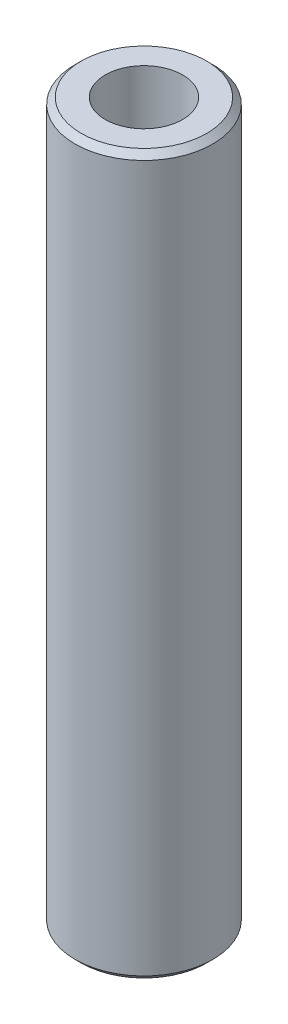
SolidWorks part; units mm, degrees
ref_plane "Front Plane" through (0, 0, 0) normal (0, 0, 1) x (1, 0, 0)
ref_plane "Top Plane" through (0, 0, 0) normal (0, 1, 0) x (1, 0, 0)
ref_plane "Right Plane" through (0, 0, 0) normal (1, 0, 0) x (0, 0, -1)
sketch "Sketch1" plane through (0, 0, 0) normal (0, 1, 0) x (1, 0, 0)
  circle A0 centre (0, 0) radius 57.5
  dimension "SHAFT_OD" = 115
extrude "Boss-Extrude1" add sketch "Sketch1" along normal blind 600
sketch "Sketch2" plane through (0, 0, 0) normal (0, 1, 0) x (1, 0, 0)
  circle A0 centre (0, 0) radius 32.3205
  dimension "BORE_D" = 64.6411
extrude "Cut-Extrude1" cut sketch "Sketch2" along normal through all
chamfer "Chamfer1" distance 5.1136 angle 45 2 edges at (0, 600, 57.5) (0, 0, 57.5)
